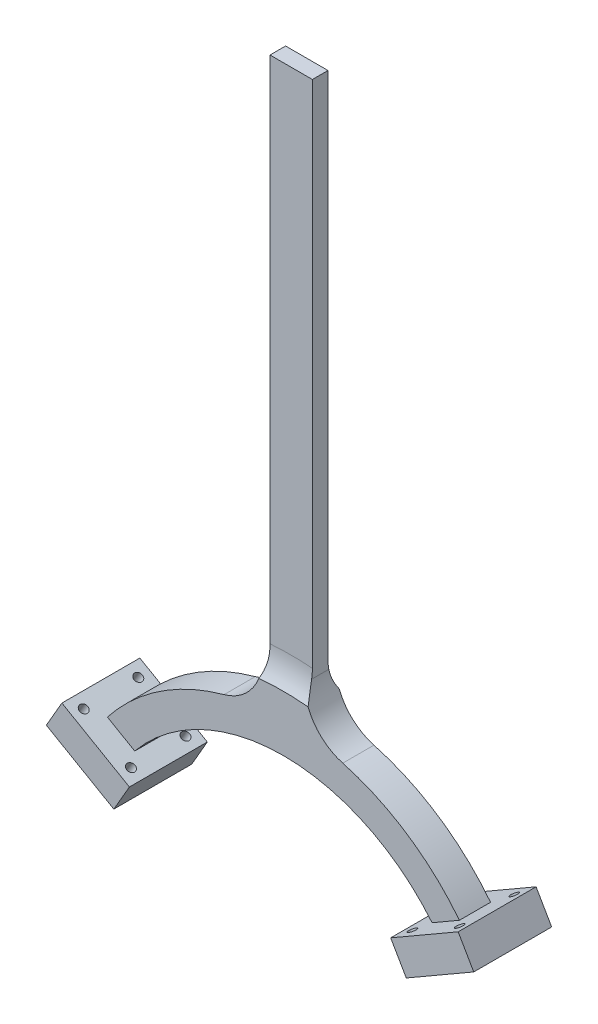
SolidWorks part; units mm, degrees
material "6063-T5"
ref_plane "Front Plane" through (0, 0, 0) normal (0, 0, 1) x (1, 0, 0)
ref_plane "Top Plane" through (0, 0, 0) normal (0, 1, 0) x (1, 0, 0)
ref_plane "Right Plane" through (0, 0, 0) normal (1, 0, 0) x (0, 0, -1)
sketch "Sketch1" plane through (0, 0, 0) normal (0, 1, 0) x (1, 0, 0)
  circle A0 centre (0, 0) radius 8.2
  dimension "D1" = 16.4
extrude "Boss-Extrude1" add sketch "Sketch1" along normal blind 25 contours A0
sketch "Sketch2" plane through (0, 0, 0) normal (0, -1, 0) x (-1, 0, 0)
  line L0 (-20.395, -7.5) -> (20.395, -7.5)
  line L1 (-20.395, -7.5) -> (-20.395, 7.5)
  line L2 (20.395, -7.5) -> (20.395, 7.5)
  line L3 (-20.395, 7.5) -> (20.395, 7.5)
  line L4 (-20.395, -7.5) -> (20.395, 7.5) construction
  line L5 (20.395, -7.5) -> (-20.395, 7.5) construction
  point P1 (0, 0)
  dimension "D1" = 40.79
  dimension "D2" = 15
extrude "Boss-Extrude2" add sketch "Sketch2" along normal blind 25
sketch "Sketch3" plane through (0, -25, 0) normal (0, -1, 0) x (-1, 0, 0)
  circle A0 centre (0, 0) radius 12.5
  dimension "D1" = 25
extrude "Boss-Extrude4" add sketch "Sketch3" against normal up to surface (25 mm away) up to face at (-13.0763, 0, 0)
sketch "Sketch4" plane through (-20.395, 0, 0) normal (-1, 0, 0) x (0, 0, 1)
  line L0 (7.5, -25) -> (207.5, -25)
  line L1 (207.5, -25) -> (207.5, -225)
  line L2 (207.5, -225) -> (7.5, -25)
  line L3 (207.5, -225) -> (192.5, -225)
  line L5 (192.5, -225) -> (-7.5, -25)
  line L6 (-7.5, -25) -> (7.5, -25)
  line M7 (-7.5, -25) -> (7.5, -25)
  dimension "D1" = 200
  dimension "D2" = 200
  dimension "D3" = 15
extrude "Boss-Extrude5" add sketch "Sketch4" against normal up to surface (40.79 mm away) contours L5 L3 L2 M7 region at (-20.395, -125, 100) up to face at (20.395, -12.5, 0)
sketch "Sketch5" plane through (0, -225, 0) normal (0, -1, 0) x (-1, 0, 0)
  line L1 (-20.395, -207.5) -> (20.395, -207.5)
  line L2 (-20.395, -207.5) -> (-20.395, -192.5)
  line L3 (-20.395, -192.5) -> (20.395, -192.5)
  line L4 (20.395, -207.5) -> (20.395, -192.5)
extrude "Boss-Extrude7" add sketch "Sketch5" along normal blind 1505
sketch "Sketch7" plane through (20.395, 0, 0) normal (1, 0, 0) x (0, 0, -1)
  line L0 (-7.5, -25) -> (0, -32.5)
  line L1 (7.5, -25) -> (-192.5, -225) construction
  line L2 (0, -32.5) -> (1.5521, -34.0521)
  line L3 (-7.5, -25) -> (-9.0521, -23.4479)
  line L4 (-9.0521, -23.4479) -> (-7.5, -21.8958)
  line L5 (-7.5, -25) -> (-7.5, 0) construction
  line L6 (1.5521, -34.0521) -> (7.5, -28.1042)
  line L7 (7.5, -28.1042) -> (7.5, -25)
  line L8 (1.5521, -34.0521) -> (-192.5, -228.1042)
  line L9 (-192.5, -1730) -> (-192.5, -225) construction
  line L10 (-192.5, -228.1042) -> (-192.5, -225)
  line L11 (-192.5, -225) -> (7.5, -25)
  line L12 (-9.0521, -23.4479) -> (-207.5, -221.8958)
  line L13 (-207.5, -221.8958) -> (-207.5, -225)
  line L14 (-207.5, -225) -> (-7.5, -25)
  line L15 (-7.5, -21.8958) -> (-7.5, -25)
  line M3 (-7.5, 0) -> (-7.5, -25)
  line M4 (-7.5, -25) -> (-207.5, -225)
  line M6 (-192.5, -225) -> (7.5, -25)
  line M12 (-192.5, -1730) -> (-192.5, -225)
  dimension "D1" = 10.6066
  dimension "D2" = 2.195
  dimension "D3" = 2.195
extrude "Boss-Extrude8" add sketch "Sketch7" against normal up to surface (40.79 mm away) contours L8 L2 M6 M12 | L6 L7 L2 M6 | L12 L13 L3 M4 | L4 L3 M3 region at (20.395, -29.8693, -4.1231) region at (20.395, -129.9156, 95.8615) region at (20.395, -123.8374, 107.8875) region at (20.395, -23.4479, 8.0174) up to face at (-20.395, -495, 100)
ref_plane "Plane4" through (0, 0, 0) normal (1, 0, 0) x (0, 0, -1)
ref_axis "Axis1" through (0, -1730, 192.5) along (0, 0, 1)
sketch "Sketch9" plane through (0, 0, 0) normal (1, 0, 0) x (0, 0, -1)
  line L0 (0, 0) -> (0, -1530)
  line L1 (0, -1530) -> (-200, -1530)
  line L2 (-200, -1530) -> (-200, -1515)
  line L3 (-200, -1515) -> (-185, -1515)
  line L4 (-200, -1530) -> (-215, -1530)
  line L5 (-215, -1530) -> (-215, -1545)
  line L7 (-215, -1545) -> (-185, -1545)
  line L8 (-215, -1545) -> (-215, -1515)
  line L9 (-215, -1515) -> (-185, -1515)
  line L10 (-185, -1545) -> (-185, -1515)
  dimension "D1" = 1530
  dimension "D2" = 200
  dimension "D3" = 15
  dimension "D4" = 15
  dimension "D5" = 15
  dimension "D6" = 15
revolve "Revolve1" add sketch "Sketch9" angle 60 about axis through (0, -1730, 192.5) along (0, 0, 1) region at (0, -1537.5, 200) region at (0, -1522.5, 192.5) region at (0, -1522.5, 207.5) other way angle 60
fillet "Fillet3" radius 50 4 edges at (20.395, -1515.9695, 200) (-20.395, -1515.9695, 200) (0, -1515, 192.5) (0, -1515, 207.5) type face fillet first side face at (0, -1568.75, 200) second side face at (-20.395, -441.4924, 100) second side face at (0, -868.6903, 207.5) second side face at (20.395, -441.4924, 100) second side face at (0, -871.7945, 192.5)
sketch "Sketch11" plane through (749.112, -1297.5, 0) normal (0.5, -0.866, 0) x (-0.866, -0.5, 0)
  line L0 (665, -185) -> (665, -215)
  line L1 (680, -185) -> (650, -185) construction
  line L2 (680, -215) -> (650, -215) construction
  line L3 (627.5, -237.5) -> (702.5, -237.5)
  line L4 (627.5, -237.5) -> (627.5, -162.5)
  line L5 (702.5, -237.5) -> (702.5, -162.5)
  line L6 (627.5, -162.5) -> (702.5, -162.5)
  line L7 (627.5, -237.5) -> (702.5, -162.5) construction
  line L8 (702.5, -237.5) -> (627.5, -162.5) construction
  line L9 (665, -200) -> (650, -185)
  line L10 (650, -185) -> (627.5, -162.5)
  circle A0 centre (638.75, -173.75) radius 4
  circle A1 centre (691.25, -173.75) radius 4
  circle A2 centre (691.25, -226.25) radius 4
  circle A3 centre (638.75, -226.25) radius 4
  point P7 (665, -200)
  point P25 (665, -200)
  line M1 (650, -185) -> (650, -215)
  line M2 (650, -215) -> (680, -215)
  line M3 (680, -215) -> (680, -185)
  line M4 (680, -185) -> (650, -185)
  dimension "D3" = 8
  dimension "D1" = 75
  dimension "D2" = 75
  dimension "D4" = 4
extrude "Boss-Extrude9" add sketch "Sketch11" against normal blind 30 contours A0 L4 L3 L5 L6 A3 A2 A1 M4 M3 M2 M1 | L0 L9 M1 M2 | L9 L0 M4 | L0 M4 M2 M3 region at (166.7099, -1633.75, 200) region at (173.2051, -1630, 163.5607) region at (177.5352, -1627.5, 190) region at (180.422, -1625.8333, 203.3333)
mirror "Mirror1" about plane through (0, 0, 0) normal (1, 0, 0) of "Boss-Extrude9"
sketch "Sketch15" plane through (0, 0, 192.5) normal (0, 0, -1) x (-1, 0, 0)
  line L0 (-20.395, -1730) -> (-20.395, -1546.1276)
  line L1 (20.395, -1546.1276) -> (20.395, -1730)
  line L2 (20.395, -1730) -> (-20.395, -1730)
  arc A0 (-20.395, -1546.1276) -> (20.395, -1546.1276) centre (0, -1730) cw
extrude "Cut-Extrude2" cut sketch "Sketch15" against normal through all
ref_plane "Plane5" through (0, -975, 0) normal (0, 1, 0) x (1, 0, 0)
sketch "Sketch16" plane through (0, -975, 0) normal (0, 1, 0) x (1, 0, 0)
  circle A0 centre (0, 0) radius 677.8594
extrude "Cut-Extrude3" cut sketch "Sketch16" along normal through all
ref_plane "Plane6" through (0, 0, 200) normal (0, 0, -1) x (-1, 0, 0)
